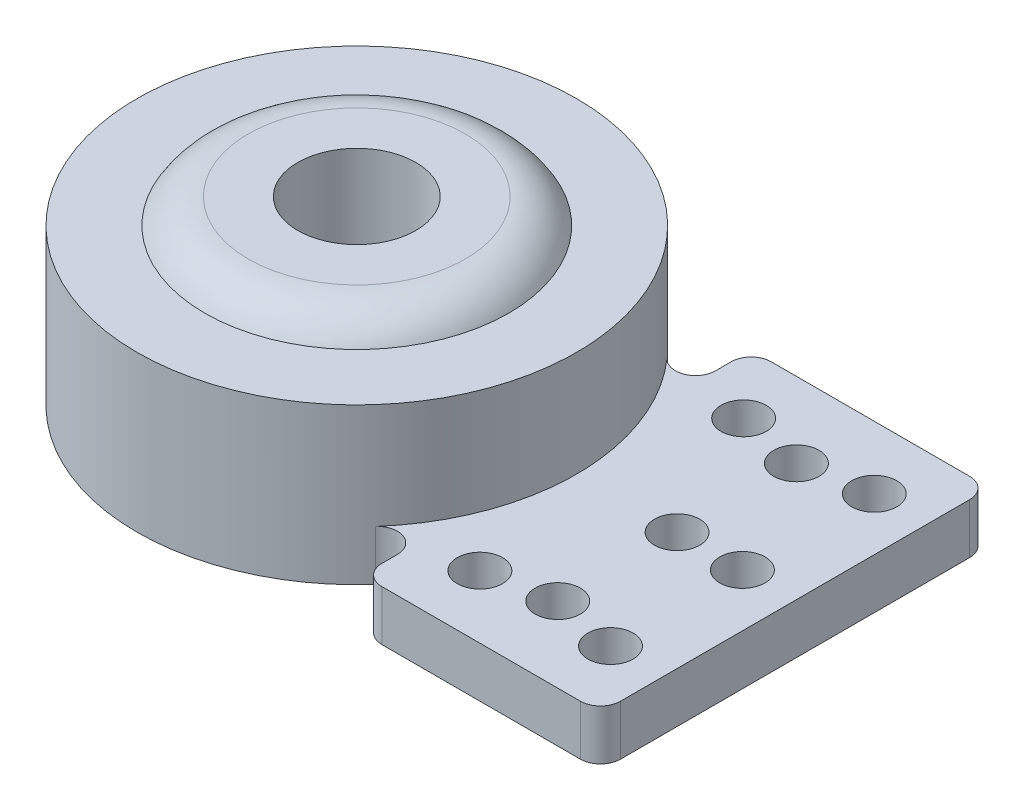
SolidWorks part; units mm, degrees
ref_plane "Front" through (0, 0, 0) normal (0, 0, 1) x (1, 0, 0)
ref_plane "Top" through (0, 0, 0) normal (0, 1, 0) x (1, 0, 0)
ref_plane "Right" through (0, 0, 0) normal (1, 0, 0) x (0, 0, -1)
sketch "Sketch1" plane through (0, 0, 0) normal (0, 1, 0) x (1, 0, 0)
  circle A0 centre (0, 0) radius 8.75
  dimension "D1" = 17.5
extrude "Boss-Extrude1" add sketch "Sketch1" along normal blind 6.2
sketch "Sketch2" plane through (0, 0, 0) normal (0, -1, 0) x (1, 0, 0)
  line L0 (-8.75, 0) -> (17.45, 0)
  line L1 (17.45, -7.75) -> (17.45, 7.75)
  line L3 (17.45, -7.75) -> (7.95, -7.75)
  line L4 (17.45, -7.75) -> (17.45, 7.75)
  line L5 (17.45, 7.75) -> (7.95, 7.75)
  line L6 (7.95, -7.75) -> (7.95, 7.75)
  line L7 (17.45, -7.75) -> (7.95, 7.75) construction
  line L8 (17.45, 7.75) -> (7.95, -7.75) construction
  circle A0 centre (0, 0) radius 8.75 construction
  point P9 (17.45, 0)
  point P11 (12.7, 0)
  circle M4 centre (0, 0) radius 8.75
  dimension "D1" = 26.2
  dimension "D2" = 15.5
  dimension "D3" = 9.5
extrude "Boss-Extrude2" add sketch "Sketch2" against normal blind 2 contours L6 L0 L1 L5 M4 | L6 L3 L1 L0 M4 region at (12.8216, 0, 3.9435) region at (12.8216, 0, -3.9435)
fillet "Fillet1" radius 0.8 6 edges at (7.95, 1, -3.6551) (7.95, 1, 3.6551) (17.45, 1, 7.75) (7.95, 1, 7.75) (17.45, 1, -7.75) (7.95, 1, -7.75)
sketch "Sketch3" plane through (0, 0, 0) normal (0, -1, 0) x (1, 0, 0)
  circle A0 centre (0, 0) radius 4.75
  dimension "D1" = 9.5
extrude "Boss-Extrude3" add sketch "Sketch3" along normal blind 1.3
sketch "Sketch4" plane through (0, -1.3, 0) normal (0, -1, 0) x (1, 0, 0)
  circle A0 centre (0, 0) radius 2.35
  dimension "D1" = 4.7
sketch "Sketch6" plane through (0, 6.2, 0) normal (0, 1, 0) x (1, 0, 0)
  circle A0 centre (0, 0) radius 6.05
  dimension "D1" = 12.1
extrude "Boss-Extrude5" add sketch "Sketch6" along normal blind 1
extrude "Cut-Extrude2" cut sketch "Sketch4" against normal through all
fillet "Fillet2" radius 2 1 edges at (0, 7.2, 6.05)
sketch "Sketch7" plane through (0, 0, 0) normal (0, -1, 0) x (1, 0, 0)
  line L0 (15.35, -7.75) -> (15.35, -5.25)
  line L1 (16.65, -7.75) -> (8.75, -7.75) construction
  line L2 (15.35, -5.25) -> (17.45, -5.25)
  line L3 (17.45, -6.95) -> (17.45, 6.95) construction
  line L5 (15.35, -5.25) -> (10.15, -5.25)
  line L6 (12.75, -5.25) -> (12.75, -4.75)
  line L7 (50, 0) -> (-50, 0) construction
  line L8 (12.75, -4.75) -> (12.75, 4.75)
  line L9 (15.35, 5.25) -> (15.35, -5.25)
  circle A0 centre (15.35, -5.25) radius 0.9
  circle A1 centre (10.15, -5.25) radius 0.9
  circle A2 centre (12.75, -4.75) radius 0.9
  circle A3 centre (15.35, 5.25) radius 0.9
  circle A4 centre (12.75, 4.75) radius 0.9
  circle A5 centre (10.15, 5.25) radius 0.9
  circle A6 centre (15.35, 0) radius 0.9
  circle A7 centre (12.75, 0) radius 0.9
  dimension "D3" = 1.8
  dimension "D5" = 1.8
  dimension "D7" = 1.8
  dimension "D8" = 1.8
  dimension "D9" = 1.8
  dimension "D1" = 2.1
  dimension "D2" = 2.5
  dimension "D4" = 5.2
  dimension "D6" = 0.5
extrude "Cut-Extrude4" cut sketch "Sketch7" against normal blind 10 contours A1 | L8 A7 | L8 A7 | A4 | A5 | A3 | L9 A6 | L9 A6 | L6 A2 L8 | L8 A2 L6 | L9 A0 L5 | L2 A0 L9 | L0 A0 L2 | L5 A0 L0 | A2 region at (14.968, 0, -5.632) region at (9.2755, 0, -5.25) region at (12.1316, 0, 5.3684) region at (12.368, 0, 0) region at (13.132, 0, 0) region at (13.1499, 0, -4.6184) region at (14.7316, 0, 5.8684) region at (14.968, 0, 0) region at (15.732, 0, 0) region at (15.732, 0, -5.632) region at (15.732, 0, -4.868) region at (14.968, 0, -4.868) region at (12.3501, 0, -4.6184) region at (10.15, 0, 5.25)
